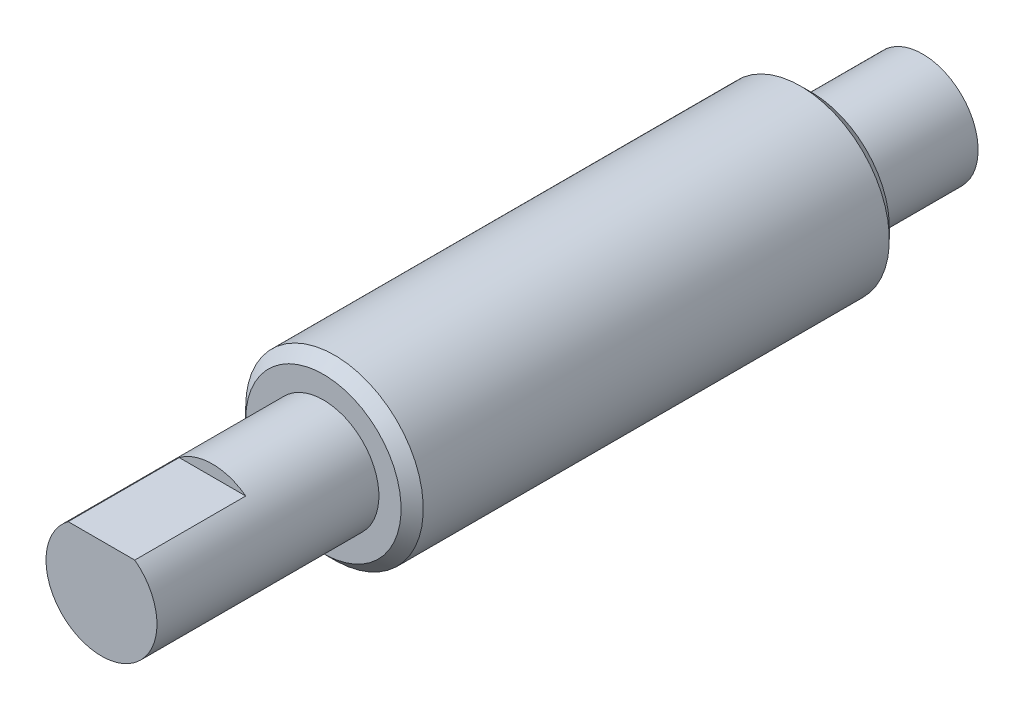
SolidWorks part; units mm, degrees
material "AISI 1020"
ref_plane "Front Plane" through (0, 0, 0) normal (0, 0, 1) x (1, 0, 0)
ref_plane "Top Plane" through (0, 0, 0) normal (0, 1, 0) x (1, 0, 0)
ref_plane "Right Plane" through (0, 0, 0) normal (1, 0, 0) x (0, 0, -1)
sketch "Sketch1" plane through (0, 0, 0) normal (0, 1, 0) x (1, 0, 0)
  line L0 (0, 74) -> (0, 0)
  line L1 (0, 0) -> (5, 0)
  line L2 (5, 0) -> (5, 20)
  line L3 (5, 20) -> (7, 20)
  line L4 (8, 21) -> (8, 63)
  line L5 (7, 64) -> (5, 64)
  line L6 (5, 64) -> (5, 74)
  line L7 (5, 74) -> (0, 74)
  line L8 (8, 63) -> (7, 64)
  line L9 (7, 20) -> (8, 21)
  point P6 (8, 20)
  point P7 (8, 64)
  dimension "D1" = 74
  dimension "D2" = 20
  dimension "D3" = 10
  dimension "D4" = 5
  dimension "D5" = 5
  dimension "D6" = 8
revolve "Revolve1" add sketch "Sketch1" angle 360 about L0
sketch "Sketch2" plane through (0, 0, 0) normal (0, 0, 1) x (1, 0, 0)
  line L0 (-3, 4) -> (3, 4)
  circle A0 centre (0, 0) radius 5 construction
  circle A1 centre (0, 0) radius 5 construction
  arc A2 (3, 4) -> (-3, 4) centre (0, 0) ccw
  dimension "D1" = 4
extrude "Cut-Extrude1" cut sketch "Sketch2" against normal blind 10
